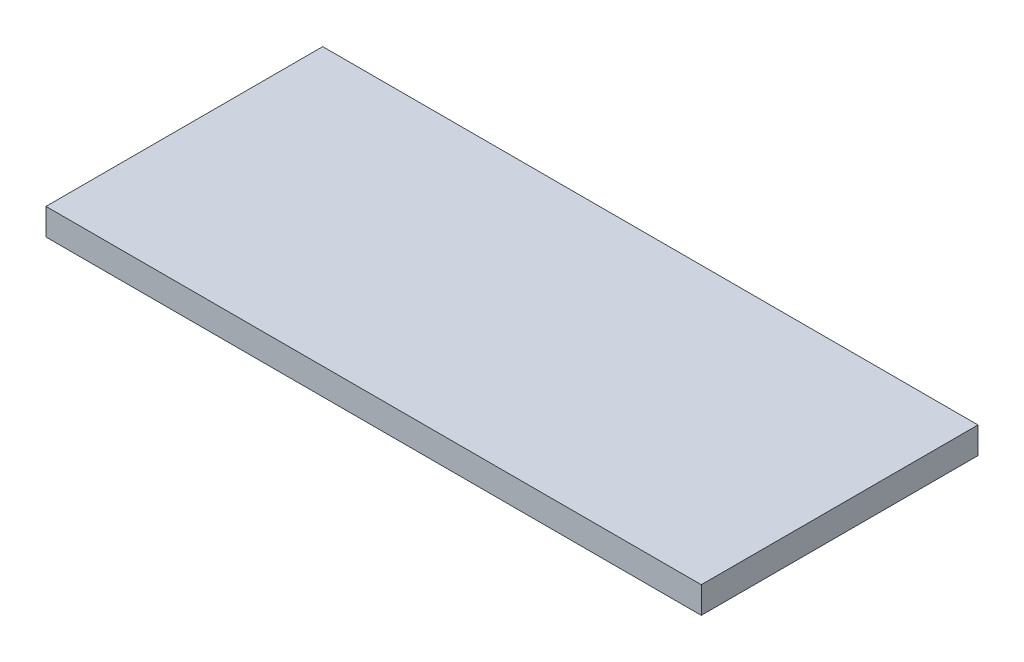
SolidWorks part; units mm, degrees
material "Plain Carbon Steel"
ref_plane "Front Plane" through (0, 0, 0) normal (0, 0, 1) x (1, 0, 0)
ref_plane "Top Plane" through (0, 0, 0) normal (0, 1, 0) x (1, 0, 0)
ref_plane "Right Plane" through (0, 0, 0) normal (1, 0, 0) x (0, 0, -1)
sketch "Sketch1" plane through (0, 0, 0) normal (0, 1, 0) x (1, 0, 0)
  line L0 (0, -55) -> (0, 55) construction
  line L1 (-74, 62.5) -> (74, 62.5)
  line L2 (-74, 62.5) -> (-74, 0)
  line L3 (-74, 0) -> (74, 0)
  line L4 (74, 62.5) -> (74, 0)
  line L5 (-74, 62.5) -> (74, 0) construction
  line L6 (-74, 0) -> (74, 62.5) construction
  line L7 (-55, 0) -> (55, 0) construction
  point P0 (0, 31.25)
  dimension "D1" = 148
  dimension "D2" = 62.5
extrude "Boss-Extrude1" add sketch "Sketch1" along normal blind 6
sketch "Sketch2" plane through (0, 0, 0) normal (0, 1, 0) x (1, 0, 0)
  line L0 (0, -55) -> (0, 55) construction
  line L1 (74, 62.5) -> (-74, 62.5) construction
  circle A0 centre (20, 52.5) radius 3.3
  circle A1 centre (-20, 52.5) radius 3.3
  dimension "D1" = 20
  dimension "D2" = 6.6
  dimension "D3" = 10
extrude "Cut-Extrude1" [suppressed] cut sketch "Sketch2" along normal through all
sketch "Sketch3" plane through (0, 0, 0) normal (0, 1, 0) x (1, 0, 0)
  line L0 (74, 62.5) -> (-74, 62.5) construction
  line L2 (0, -3.3) -> (0, 3.3) construction
  circle A0 centre (0, -37.5) radius 82.9593
  point P5 (0, 0)
  point P8 (0, 0)
  dimension "D1" = 100
extrude "Cut-Extrude2" [suppressed] cut sketch "Sketch3" along normal through all
